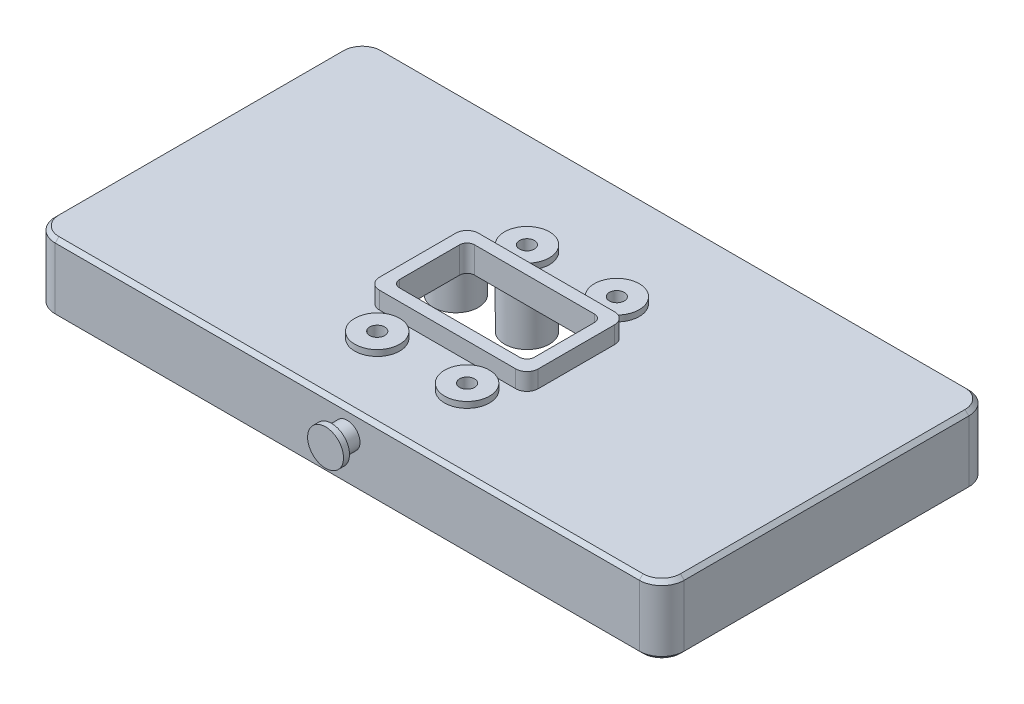
SolidWorks part; units mm, degrees
ref_plane "Front Plane" through (0, 0, 0) normal (0, 0, 1) x (1, 0, 0)
ref_plane "Top Plane" through (0, 0, 0) normal (0, 1, 0) x (1, 0, 0)
ref_plane "Right Plane" through (0, 0, 0) normal (1, 0, 0) x (0, 0, -1)
sketch "Sketch1" plane through (0, 0, 0) normal (0, 1, 0) x (1, 0, 0)
  line L0 (-39, -36) -> (39, -36)
  line L1 (42, -39) -> (42, -77)
  line L2 (39, -80) -> (-39, -80)
  line L3 (-42, -77) -> (-42, -39)
  arc A0 (-42, -39) -> (-39, -36) centre (-39, -39) cw
  arc A1 (39, -36) -> (42, -39) centre (39, -39) cw
  arc A2 (42, -77) -> (39, -80) centre (39, -77) cw
  arc A3 (-39, -80) -> (-42, -77) centre (-39, -77) cw
extrude "Boss-Extrude1" add sketch "Sketch1" along normal blind 9.2 from offset 50
chamfer "Chamfer1" distance 0.5 angle 45 8 edges at (0, 50, 36) (-41.1213, 50, 36.8787) (41.1213, 50, 36.8787) (-42, 50, 58) (42, 50, 58) (-41.1213, 50, 79.1213) (41.1213, 50, 79.1213) (0, 50, 80)
chamfer "Chamfer2" distance 0.5 angle 45 8 edges at (0, 59.2, 36) (-41.1213, 59.2, 36.8787) (41.1213, 59.2, 36.8787) (-42, 59.2, 58) (42, 59.2, 58) (-41.1213, 59.2, 79.1213) (41.1213, 59.2, 79.1213) (0, 59.2, 80)
sketch "Sketch2" plane through (0, 0, 0) normal (0, 1, 0) x (1, 0, 0)
  line L0 (-39, -37.6) -> (39, -37.6)
  line L1 (40.4, -39) -> (40.4, -77)
  line L2 (39, -78.4) -> (-39, -78.4)
  line L3 (-40.4, -77) -> (-40.4, -39)
  arc A0 (-40.4, -39) -> (-39, -37.6) centre (-39, -39) cw
  arc A1 (39, -37.6) -> (40.4, -39) centre (39, -39) cw
  arc A2 (40.4, -77) -> (39, -78.4) centre (39, -77) cw
  arc A3 (-39, -78.4) -> (-40.4, -77) centre (-39, -77) cw
extrude "Boss-Extrude2" add sketch "Sketch2" along normal blind 9 from offset 49 separate body
combine bodies "Combine1" operation type subtract main body 101 bodies to subtract 102
sketch "Sketch3" plane through (0, 0, 0) normal (0, 1, 0) x (1, 0, 0)
  circle A0 centre (-15, -50.5) radius 3
extrude "Boss-Extrude3" add sketch "Sketch3" along normal blind 8.01 from offset 50
sketch "Sketch4" plane through (0, 0, 0) normal (0, 1, 0) x (1, 0, 0)
  circle A0 centre (-15, -50.5) radius 1
extrude "Boss-Extrude4" add sketch "Sketch4" along normal blind 9.4 from offset 49 separate body
combine bodies "Combine2" operation type subtract main body 104 bodies to subtract 105
sketch "Sketch5" plane through (0, 0, 0) normal (0, 1, 0) x (1, 0, 0)
  circle A0 centre (-15, -69.5) radius 3
extrude "Boss-Extrude5" add sketch "Sketch5" along normal blind 8.01 from offset 50
sketch "Sketch6" plane through (0, 0, 0) normal (0, 1, 0) x (1, 0, 0)
  circle A0 centre (-15, -69.5) radius 1
extrude "Boss-Extrude6" add sketch "Sketch6" along normal blind 9.4 from offset 49 separate body
combine bodies "Combine3" operation type subtract main body 107 bodies to subtract 108
sketch "Sketch7" plane through (0, 0, 0) normal (0, 1, 0) x (1, 0, 0)
  circle A0 centre (15, -50.5) radius 3
extrude "Boss-Extrude7" add sketch "Sketch7" along normal blind 8.01 from offset 50
sketch "Sketch8" plane through (0, 0, 0) normal (0, 1, 0) x (1, 0, 0)
  circle A0 centre (15, -50.5) radius 1
extrude "Boss-Extrude8" add sketch "Sketch8" along normal blind 9.4 from offset 49 separate body
combine bodies "Combine4" operation type subtract main body 110 bodies to subtract 111
sketch "Sketch9" plane through (0, 0, 0) normal (0, 1, 0) x (1, 0, 0)
  circle A0 centre (15, -69.5) radius 3
extrude "Boss-Extrude9" add sketch "Sketch9" along normal blind 8.01 from offset 50
sketch "Sketch10" plane through (0, 0, 0) normal (0, 1, 0) x (1, 0, 0)
  circle A0 centre (15, -69.5) radius 1
extrude "Boss-Extrude10" add sketch "Sketch10" along normal blind 9.4 from offset 49 separate body
combine bodies "Combine5" operation type subtract main body 113 bodies to subtract 114
sketch "Sketch11" plane through (0, 0, 0) normal (0, 1, 0) x (1, 0, 0)
  circle A0 centre (-6, -50) radius 3
extrude "Boss-Extrude11" add sketch "Sketch11" along normal blind 10 from offset 50
sketch "Sketch12" plane through (0, 0, 0) normal (0, 1, 0) x (1, 0, 0)
  circle A0 centre (-6, -50) radius 1
extrude "Boss-Extrude12" add sketch "Sketch12" along normal blind 9.5 from offset 51.5 separate body
combine bodies "Combine6" operation type subtract main body 116 bodies to subtract 117
sketch "Sketch13" plane through (0, 0, 0) normal (0, 1, 0) x (1, 0, 0)
  circle A0 centre (-6, -70) radius 3
extrude "Boss-Extrude13" add sketch "Sketch13" along normal blind 10 from offset 50
sketch "Sketch14" plane through (0, 0, 0) normal (0, 1, 0) x (1, 0, 0)
  circle A0 centre (-6, -70) radius 1
extrude "Boss-Extrude14" add sketch "Sketch14" along normal blind 9.5 from offset 51.5 separate body
combine bodies "Combine7" operation type subtract main body 119 bodies to subtract 120
sketch "Sketch15" plane through (0, 0, 0) normal (0, 1, 0) x (1, 0, 0)
  circle A0 centre (6, -50) radius 3
extrude "Boss-Extrude15" add sketch "Sketch15" along normal blind 10 from offset 50
sketch "Sketch16" plane through (0, 0, 0) normal (0, 1, 0) x (1, 0, 0)
  circle A0 centre (6, -50) radius 1
extrude "Boss-Extrude16" add sketch "Sketch16" along normal blind 9.5 from offset 51.5 separate body
combine bodies "Combine8" operation type subtract main body 122 bodies to subtract 123
sketch "Sketch17" plane through (0, 0, 0) normal (0, 1, 0) x (1, 0, 0)
  circle A0 centre (6, -70) radius 3
extrude "Boss-Extrude17" add sketch "Sketch17" along normal blind 10 from offset 50
sketch "Sketch18" plane through (0, 0, 0) normal (0, 1, 0) x (1, 0, 0)
  circle A0 centre (6, -70) radius 1
extrude "Boss-Extrude18" add sketch "Sketch18" along normal blind 9.5 from offset 51.5 separate body
combine bodies "Combine9" operation type subtract main body 125 bodies to subtract 126
sketch "Sketch19" plane through (0, 0, 0) normal (0, 0, 1) x (1, 0, 0)
  circle A0 centre (0, 56) radius 1.7
extrude "Boss-Extrude19" add sketch "Sketch19" along normal blind 3.71 from offset 78.39
sketch "Sketch20" plane through (0, 0, 0) normal (0, 0, 1) x (1, 0, 0)
  circle A0 centre (0, 56) radius 2.4
extrude "Boss-Extrude20" add sketch "Sketch20" along normal blind 0.8 from offset 82.1
sketch "Sketch21" plane through (0, 0, 0) normal (0, 1, 0) x (1, 0, 0)
  line L0 (-38.99, -37.59) -> (38.99, -37.59)
  line L1 (40.39, -38.99) -> (40.39, -77.01)
  line L2 (38.99, -78.41) -> (-38.99, -78.41)
  line L3 (-40.39, -77.01) -> (-40.39, -38.99)
  line L4 (-33.6, -39.6) -> (33.6, -39.6)
  line L5 (34.6, -40.6) -> (34.6, -71.6)
  line L6 (33.6, -72.6) -> (-33.6, -72.6)
  line L7 (-34.6, -71.6) -> (-34.6, -40.6)
  arc A0 (-40.39, -38.99) -> (-38.99, -37.59) centre (-38.99, -38.99) cw
  arc A1 (38.99, -37.59) -> (40.39, -38.99) centre (38.99, -38.99) cw
  arc A2 (40.39, -77.01) -> (38.99, -78.41) centre (38.99, -77.01) cw
  arc A3 (-38.99, -78.41) -> (-40.39, -77.01) centre (-38.99, -77.01) cw
  arc A4 (-34.6, -40.6) -> (-33.6, -39.6) centre (-33.6, -40.6) cw
  arc A5 (33.6, -39.6) -> (34.6, -40.6) centre (33.6, -40.6) cw
  arc A6 (34.6, -71.6) -> (33.6, -72.6) centre (33.6, -71.6) cw
  arc A7 (-33.6, -72.6) -> (-34.6, -71.6) centre (-33.6, -71.6) cw
extrude "Boss-Extrude21" add sketch "Sketch21" along normal blind 1.2 from offset 50
sketch "Sketch22" plane through (0, 0, 0) normal (0, 1, 0) x (1, 0, 0)
  line L0 (-9.1, -53.4) -> (9.1, -53.4)
  line L1 (10.6, -54.9) -> (10.6, -65.1)
  line L2 (9.1, -66.6) -> (-9.1, -66.6)
  line L3 (-10.6, -65.1) -> (-10.6, -54.9)
  arc A0 (-10.6, -54.9) -> (-9.1, -53.4) centre (-9.1, -54.9) cw
  arc A1 (9.1, -53.4) -> (10.6, -54.9) centre (9.1, -54.9) cw
  arc A2 (10.6, -65.1) -> (9.1, -66.6) centre (9.1, -65.1) cw
  arc A3 (-9.1, -66.6) -> (-10.6, -65.1) centre (-9.1, -65.1) cw
extrude "Boss-Extrude22" add sketch "Sketch22" along normal blind 3.51 from offset 57.99
sketch "Sketch23" plane through (0, 0, 0) normal (0, 1, 0) x (1, 0, 0)
  line L0 (-8, -55) -> (8, -55)
  line L1 (9, -56) -> (9, -64)
  line L2 (8, -65) -> (-8, -65)
  line L3 (-9, -64) -> (-9, -56)
  arc A0 (-9, -56) -> (-8, -55) centre (-8, -56) cw
  arc A1 (8, -55) -> (9, -56) centre (8, -56) cw
  arc A2 (9, -64) -> (8, -65) centre (8, -64) cw
  arc A3 (-8, -65) -> (-9, -64) centre (-8, -64) cw
extrude "Boss-Extrude23" add sketch "Sketch23" along normal blind 13 from offset 49 separate body
combine bodies "Combine10" operation type subtract main body 131 bodies to subtract 132
